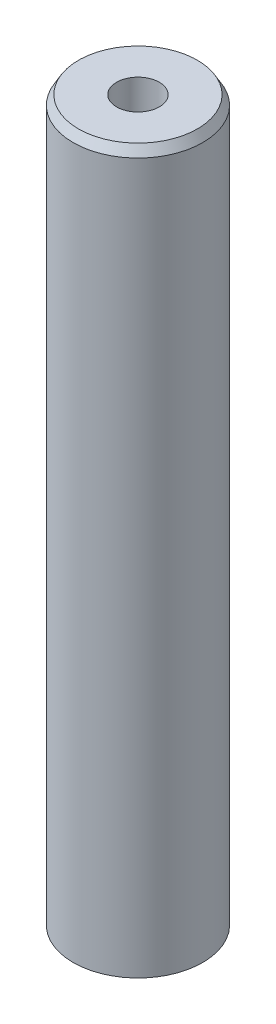
SolidWorks part; units mm, degrees
ref_plane "Front Plane" through (0, 0, 0) normal (0, 0, 1) x (1, 0, 0)
ref_plane "Top Plane" through (0, 0, 0) normal (0, 1, 0) x (1, 0, 0)
ref_plane "Right Plane" through (0, 0, 0) normal (1, 0, 0) x (0, 0, -1)
sketch "Sketch1" plane through (0, 0, 0) normal (0, 1, 0) x (1, 0, 0)
  circle A0 centre (0, 0) radius 10
  dimension "SHAFT_OD" = 20
extrude "Boss-Extrude1" add sketch "Sketch1" along normal blind 111.815
sketch "Sketch2" plane through (0, 0, 0) normal (0, 1, 0) x (1, 0, 0)
  circle A0 centre (0, 0) radius 3.2995
  dimension "BORE_D" = 6.599
extrude "Cut-Extrude1" cut sketch "Sketch2" along normal through all
chamfer "Chamfer1" distance 1.4204 angle 30 2 edges at (0, 111.815, 10) (0, 0, 10) first distance on face at (0, 111.815, 10) first distance on face at (0, 0, 3.2995)
